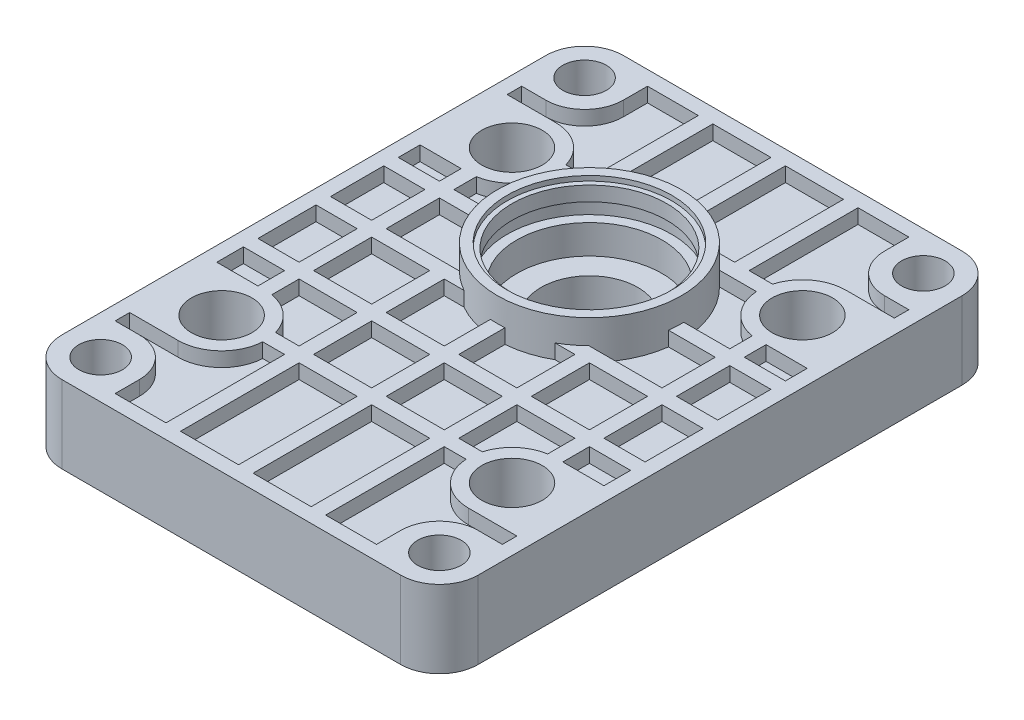
SolidWorks part; units mm, degrees
ref_plane "前视基准面" through (0, 0, 0) normal (0, 0, 1) x (1, 0, 0)
ref_plane "上视基准面" through (0, 0, 0) normal (0, 1, 0) x (1, 0, 0)
ref_plane "右视基准面" through (0, 0, 0) normal (1, 0, 0) x (0, 0, -1)
sketch "草图1" plane through (0, 0, 0) normal (0, 1, 0) x (1, 0, 0)
  line L1 (-43, 58) -> (43, 58)
  line L2 (-43, 58) -> (-43, -58)
  line L3 (-43, -58) -> (43, -58)
  line L4 (43, 58) -> (43, -58)
  line L5 (-43, 58) -> (43, -58) construction
  line L6 (-43, -58) -> (43, 58) construction
  point P0 (0, 0)
  dimension "D1" = 116
  dimension "D2" = 86
extrude "凸台-拉伸1" add sketch "草图1" along normal blind 16
sketch "草图2" plane through (0, 16, 0) normal (0, 1, 0) x (1, 0, 0)
  line L1 (-35, 50) -> (35, 50) construction
  line L2 (-35, 50) -> (-35, -50) construction
  line L3 (-35, -50) -> (35, -50) construction
  line L4 (35, 50) -> (35, -50) construction
  line L5 (-35, 50) -> (35, -50) construction
  line L6 (-35, -50) -> (35, 50) construction
  point P0 (0, 0)
  dimension "D1" = 100
  dimension "D2" = 70
hole_wizard "大小mm 暗销孔1" positions "3D草图1" profile "草图4" hole size "Ø1.0" standard "GB" end condition through all
sketch3d "3D草图1"
  point P0 (-35, 16, -50)
  point P3 (35, 16, -50)
  point P6 (-35, 16, 50)
  point P9 (35, 16, 50)
sketch "草图4" plane through (-35, 16, -50) normal (1, 0, 0) x (0, 0, 1)
  line L0 (0, 0) -> (0, 16)
  line L1 (0, 16) -> (4.5, 16)
  line L2 (4.5, 16) -> (4.5, 0)
  line L5 (4.5, 0) -> (0, 0)
  line L11 (0, -6.35) -> (0, 107.95) construction
  dimension "通孔孔直径" = 9
  dimension "通孔孔深度" = 16
sketch "草图5" plane through (0, 16, 0) normal (0, 1, 0) x (1, 0, 0)
  line L1 (-30, 30) -> (30, 30) construction
  line L2 (-30, 30) -> (-30, -30) construction
  line L3 (-30, -30) -> (30, -30) construction
  line L4 (30, 30) -> (30, -30) construction
  line L5 (-30, 30) -> (30, -30) construction
  line L6 (-30, -30) -> (30, 30) construction
  point P0 (0, 0)
  dimension "D1" = 60
hole_wizard "大小mm 暗销孔2" positions "3D草图2" profile "草图6" hole size "Ø1.0" standard "GB" end condition through all
sketch3d "3D草图2"
  point P0 (-30, 16, -30)
  point P3 (30, 16, -30)
  point P6 (30, 16, 30)
  point P9 (-30, 16, 30)
sketch "草图6" plane through (-30, 16, -30) normal (1, 0, 0) x (0, 0, 1)
  line L0 (0, 0) -> (0, 16)
  line L1 (0, 16) -> (6.25, 16)
  line L2 (6.25, 16) -> (6.25, 0)
  line L5 (6.25, 0) -> (0, 0)
  line L11 (0, -6.35) -> (0, 107.95) construction
  dimension "通孔孔直径" = 12.5
  dimension "通孔孔深度" = 16
sketch "草图7" plane through (0, 16, 0) normal (0, 1, 0) x (1, 0, 0)
  line L0 (0, 0) -> (0, 47.5) construction
  line L1 (0, 0) -> (43, 0) construction
  line L2 (43, -58) -> (43, 58) construction
  line L3 (0, -47.5) -> (0, 0) construction
  point P6 (0, -47.5)
  dimension "D1" = 95
sketch "草图9" plane through (0, 16, 0) normal (0, 1, 0) x (1, 0, 0)
  line L0 (-35, 50) -> (35, 50) construction
  line L1 (0, 50) -> (0, 16) construction
  circle A0 centre (0, 16) radius 22.5 construction
  circle A1 centre (0, 16) radius 19
  dimension "D2" = 45
  dimension "D3" = 38
  dimension "D1" = 34
extrude "凸台-拉伸2" add sketch "草图9" along normal blind 5
sketch "草图10" plane through (0, 21, 0) normal (0, 1, 0) x (1, 0, 0)
  circle A0 centre (0, 16) radius 17
  dimension "D1" = 34
extrude "切除-拉伸1" cut sketch "草图10" against normal blind 1
sketch "草图11" plane through (0, 20, 0) normal (0, 1, 0) x (1, 0, 0)
  circle A0 centre (0, 16) radius 16
  dimension "D1" = 32
extrude "切除-拉伸2" cut sketch "草图11" against normal blind 3
sketch "草图12" plane through (0, 17, 0) normal (0, 1, 0) x (1, 0, 0)
  circle A0 centre (0, 16) radius 17
  dimension "D1" = 34
extrude "切除-拉伸3" cut sketch "草图12" against normal blind 3
sketch "草图13" plane through (0, 14, 0) normal (0, 1, 0) x (1, 0, 0)
  circle A0 centre (0, 16) radius 10
  circle A1 centre (0, 16) radius 16 construction
  dimension "D1" = 20
extrude "切除-拉伸4" cut sketch "草图13" against normal through all
sketch "草图14" plane through (0, 14, 0) normal (0, 1, 0) x (1, 0, 0)
  circle A0 centre (0, 16) radius 15
  dimension "D1" = 30
extrude "切除-拉伸5" cut sketch "草图14" against normal offset from surface (6 mm away) 8 up to face at (0, 0, -6)
sketch "草图15" plane through (0, 16, 0) normal (0, 1, 0) x (1, 0, 0)
  line L0 (0, 58) -> (0, 35) construction
  line L1 (43, 58) -> (-43, 58) construction
  line L2 (-43, -58) -> (43, -58) construction
  line L3 (-1.5, 58) -> (-1.5, 34.9407)
  line L4 (1.5, 58) -> (1.5, 34.9407)
  line L5 (-15, 58) -> (-15, 27.6619)
  line L6 (15, 58) -> (15, 27.6619)
  line L7 (-16.5, 58) -> (-16.5, 25.4207)
  line L8 (13.5, 58) -> (13.5, 29.3697)
  line L9 (-13.5, 58) -> (-13.5, 29.3697)
  line L10 (16.5, 58) -> (16.5, 25.4207)
  line L11 (16.5, 6.5793) -> (16.5, -58)
  line L12 (16.5, 58) -> (16.5, -58) construction
  line L13 (15, 1) -> (15, -58) construction
  line L14 (15, 58) -> (15, -58) construction
  line L15 (13.5, 2.6303) -> (13.5, -58)
  line L16 (13.5, 58) -> (13.5, -58) construction
  line L17 (1.5, -2.9407) -> (1.5, -58)
  line L18 (1.5, 58) -> (1.5, -58) construction
  line L19 (0, -3) -> (0, -58) construction
  line L20 (0, 58) -> (0, -58) construction
  line L21 (-1.5, -2.9407) -> (-1.5, -58)
  line L22 (-1.5, 58) -> (-1.5, -58) construction
  line L23 (-13.5, 2.6303) -> (-13.5, -58)
  line L24 (-13.5, 58) -> (-13.5, -58) construction
  line L25 (-15, 4.3381) -> (-15, -58) construction
  line L26 (-15, 58) -> (-15, -58) construction
  line L27 (-16.5, 6.5793) -> (-16.5, -58)
  line L28 (-16.5, 58) -> (-16.5, -58) construction
  line L29 (43, 16) -> (19, 16) construction
  line L30 (43, -58) -> (43, 58) construction
  line L31 (-19, 16) -> (-43, 16) construction
  line L32 (-43, 58) -> (-43, -58) construction
  line L33 (-11.6619, 1) -> (-43, 1) construction
  line L34 (43, 1) -> (15, 1) construction
  line L35 (43, 1) -> (19, 1) construction
  line L36 (-19, 1) -> (-43, 1) construction
  line L37 (43, -14) -> (1.5, -14) construction
  line L38 (1.5, -14) -> (-43, -14) construction
  line L39 (1.5, -29) -> (-43, -29) construction
  line L40 (43, -29) -> (1.5, -29) construction
  line L41 (-11.6619, -29) -> (-43, -29) construction
  line L42 (-11.6619, -14) -> (-43, -14) construction
  line L43 (43, 1) -> (11.6619, 1) construction
  line L44 (-19, 17.5) -> (-43, 17.5)
  line L45 (-13.3697, 2.5) -> (-43, 2.5)
  line L46 (43, -12.5) -> (1.5, -12.5)
  line L47 (1.5, -12.5) -> (-43, -12.5)
  line L48 (43, -27.5) -> (1.5, -27.5)
  line L49 (1.5, -27.5) -> (-43, -27.5)
  line L50 (43, 2.5) -> (15, 2.5)
  line L51 (43, 17.5) -> (19, 17.5)
  line L52 (-19, 14.5) -> (-43, 14.5)
  line L53 (-9.4207, -0.5) -> (-43, -0.5)
  line L54 (43, -15.5) -> (1.5, -15.5)
  line L55 (1.5, -15.5) -> (-43, -15.5)
  line L56 (43, -30.5) -> (1.5, -30.5)
  line L57 (1.5, -30.5) -> (-43, -30.5)
  line L58 (43, -0.5) -> (15, -0.5)
  line L59 (43, 14.5) -> (19, 14.5)
  line L60 (11.6619, -15.5) -> (-43, -15.5) construction
  line L61 (11.6619, -14) -> (-43, -14) construction
  line L62 (11.6619, -12.5) -> (-43, -12.5) construction
  line L63 (43, -12.5) -> (11.6619, -12.5) construction
  line L64 (43, -14) -> (11.6619, -14) construction
  line L65 (43, -15.5) -> (11.6619, -15.5) construction
  line L66 (11.6619, -30.5) -> (-43, -30.5) construction
  line L67 (11.6619, -29) -> (-43, -29) construction
  line L68 (11.6619, -27.5) -> (-43, -27.5) construction
  line L69 (43, -27.5) -> (11.6619, -27.5) construction
  line L70 (43, -29) -> (11.6619, -29) construction
  line L71 (43, -30.5) -> (11.6619, -30.5) construction
  line L72 (-11.6619, 2.5) -> (-43, 2.5) construction
  line L73 (-11.6619, -0.5) -> (-43, -0.5) construction
  line L74 (-13.3697, 29.5) -> (-43, 29.5)
  line L75 (-11.6619, 31) -> (-43, 31) construction
  line L76 (-9.4207, 32.5) -> (-43, 32.5)
  line L77 (43, 32.5) -> (9.4207, 32.5)
  line L78 (43, 31) -> (11.6619, 31) construction
  line L79 (43, 29.5) -> (13.3697, 29.5)
  line L80 (43, 31) -> (19, 31) construction
  line L81 (-19, 31) -> (-43, 31) construction
  line L82 (43, 32.5) -> (19, 32.5) construction
  line L83 (43, 29.5) -> (19, 29.5) construction
  line L84 (-19, 29.5) -> (-43, 29.5) construction
  line L85 (-19, 32.5) -> (-43, 32.5) construction
  line L86 (40, -55) -> (40, 55)
  line L87 (40, 55) -> (-40, 55)
  line L88 (-40, 55) -> (-40, -55)
  line L89 (-40, -55) -> (40, -55)
  line L90 (43, -58) -> (43, 58)
  line L91 (43, 58) -> (-43, 58)
  line L92 (-43, 58) -> (-43, -58)
  line L93 (-43, -58) -> (43, -58)
  line L94 (43, -58) -> (43, 58)
  line L95 (43, 58) -> (-43, 58)
  line L96 (-43, 58) -> (-43, -58)
  line L97 (-43, -58) -> (43, -58)
  circle A0 centre (0, 16) radius 19 construction
  arc A1 (-16.5, 6.5793) -> (-16.5, 25.4207) centre (0, 16) ccw
  circle A2 centre (0, 16) radius 19 construction
  circle A3 centre (0, 16) radius 19
  circle A4 centre (35, 50) radius 8
  circle A5 centre (-35, 50) radius 8
  circle A6 centre (-35, -50) radius 8
  circle A7 centre (35, -50) radius 8
  dimension "D13" = 0
  dimension "D14" = 16
  dimension "D1" = 1.5
  dimension "D7" = 15
  dimension "D2" = 1.5
  dimension "D3" = 15
  dimension "D4" = 15
  dimension "D5" = 1.5
  dimension "D6" = 1.5
  dimension "D8" = 15
  dimension "D9" = 15
  dimension "D10" = 1.5
  dimension "D11" = 1.5
  dimension "D12" = 15
  dimension "D15" = 3
extrude "切除-拉伸6" cut sketch "草图15" against normal blind 3
sketch "草图16" plane through (0, 16, 0) normal (0, 1, 0) x (1, 0, 0)
  line L0 (16.5, -0.5) -> (9.4207, -0.5)
  line L1 (16.5, 2.5) -> (13.3697, 2.5)
  line L5 (1.5, -12.5) -> (13.5, -12.5)
  line L6 (13.5, -12.5) -> (13.5, 2.6303)
  line L7 (1.5, -2.9407) -> (1.5, -12.5)
  line L8 (1.5, -12.5) -> (13.5, -12.5)
  line L9 (13.5, -12.5) -> (13.5, 2.6303)
  line L10 (1.5, -2.9407) -> (1.5, -12.5)
  arc A0 (1.5, -2.9407) -> (13.5, 2.6303) centre (0, 16) ccw construction
  circle A2 centre (0, 16) radius 17
  circle A3 centre (0, 16) radius 17
  arc A4 (1.5, -2.9407) -> (13.5, 2.6303) centre (0, 16) ccw
  arc A5 (1.5, -2.9407) -> (13.5, 2.6303) centre (0, 16) ccw
  circle A6 centre (0, 16) radius 19
  circle A7 centre (0, 16) radius 19
  dimension "D1" = 0
  dimension "D2" = 0
  dimension "D3" = 0
extrude "凸台-拉伸3" add sketch "草图16" against normal blind 3 contours A5 L0 L9 L1
sketch "草图17" plane through (0, 16, 0) normal (0, 1, 0) x (1, 0, 0)
  line L0 (13.3697, 2.5) -> (16.5, 2.5)
  line L5 (43, -58) -> (43, 58)
  line L6 (16.5, 2.5) -> (40, 2.5)
  line L7 (40, 2.5) -> (40, 29.5)
  line L8 (40, 29.5) -> (36.23, 29.5)
  line L9 (23.77, 29.5) -> (13.3697, 29.5)
  line L10 (16.5, 6.5793) -> (16.5, 2.5)
  line L11 (16.5, 2.5) -> (40, 2.5)
  line L12 (40, 2.5) -> (40, 29.5)
  line L13 (40, 29.5) -> (36.23, 29.5)
  line L14 (23.77, 29.5) -> (13.3697, 29.5)
  line L15 (16.5, 6.5793) -> (16.5, 2.5)
  line L16 (43, 58) -> (-43, 58)
  line L17 (-43, 58) -> (-43, -58)
  line L18 (-43, -58) -> (43, -58)
  line L19 (43, -58) -> (43, 58)
  line L20 (43, 58) -> (-43, 58)
  line L21 (-43, 58) -> (-43, -58)
  line L22 (-43, -58) -> (43, -58)
  circle A1 centre (0, 16) radius 19
  arc A2 (23.77, 29.5) -> (36.23, 29.5) centre (30, 30) ccw
  arc A3 (16.5, 6.5793) -> (13.3697, 29.5) centre (0, 16) ccw
  arc A4 (23.77, 29.5) -> (36.23, 29.5) centre (30, 30) ccw
  arc A5 (16.5, 6.5793) -> (13.3697, 29.5) centre (0, 16) ccw
  circle A6 centre (0, 16) radius 19
  dimension "D1" = 0
  dimension "D2" = 0
  dimension "D3" = 0
extrude "切除-拉伸7" cut sketch "草图17" against normal blind 3 contours A6 L0 L15
fillet "圆角1" radius 8 4 edges at (-43, 8, -58) (43, 8, -58) (43, 8, 58) (-43, 8, 58)
sketch "草图18" plane through (0, 16, 0) normal (0, 1, 0) x (1, 0, 0)
  line L0 (-30, 39) -> (-40, 39)
  line L1 (-40, 43.755) -> (-40, 32.5) construction
  line L2 (-30, 21) -> (-40, 21)
  line L3 (-40, 29.5) -> (-40, 2.5) construction
  line L4 (0, 0) -> (0, 58) construction
  line L5 (35, 58) -> (-35, 58) construction
  line L6 (30, 21) -> (40, 21)
  line L7 (30, 39) -> (40, 39)
  line L8 (-40, 39) -> (-40, 21)
  line L9 (40, 39) -> (40, 21)
  circle A0 centre (-30, 30) radius 9
  circle A1 centre (30, 30) radius 9
  arc A2 (23.77, 29.5) -> (36.23, 29.5) centre (30, 30) ccw construction
  circle A4 centre (30, 30) radius 6.25
  circle A5 centre (-30, 30) radius 6.25
  dimension "D1" = 18
extrude "凸台-拉伸4" add sketch "草图18" against normal blind 3 contours A0 L0 L8 L2 | A1 A4 | A1 L6 L9 L7 | A0 A5
mirror "镜向1" about plane through (0, 0, 0) normal (0, 0, 1) of "凸台-拉伸4"
sketch "草图19" plane through (0, 16, 0) normal (0, 1, 0) x (1, 0, 0)
  line L0 (40, 15) -> (18.9737, 15)
  line L1 (40, 2.5) -> (40, 21) construction
  line L2 (-40, 21) -> (-40, 2.5) construction
  line L3 (-13.3697, 2.5) -> (-40, 2.5) construction
  line L4 (40, 16.5) -> (18.9934, 16.5)
  line L5 (40, 13.5) -> (18.8348, 13.5)
  line L6 (-18.8348, 13.5) -> (-40, 13.5)
  line L7 (40, 13.5) -> (-40, 13.5) construction
  line L8 (-18.9737, 15) -> (-40, 15)
  line L9 (40, 15) -> (-40, 15) construction
  line L10 (-18.9934, 16.5) -> (-40, 16.5)
  line L11 (40, 16.5) -> (-40, 16.5) construction
  line L12 (-40, 16.5) -> (-40, 13.5)
  line L13 (40, 16.5) -> (40, 13.5)
  line L16 (35, 58) -> (-35, 58)
  line L17 (-43, 50) -> (-43, -50)
  line L18 (-35, -58) -> (35, -58)
  line L19 (43, -50) -> (43, 50)
  line L20 (35, 58) -> (-35, 58)
  line L21 (-43, 50) -> (-43, -50)
  line L22 (-35, -58) -> (35, -58)
  line L23 (43, -50) -> (43, 50)
  circle A1 centre (0, 16) radius 19
  circle A2 centre (0, 16) radius 19
  arc A6 (-35, 58) -> (-43, 50) centre (-35, 50) ccw
  arc A7 (-43, -50) -> (-35, -58) centre (-35, -50) ccw
  arc A8 (35, -58) -> (43, -50) centre (35, -50) ccw
  arc A9 (43, 50) -> (35, 58) centre (35, 50) ccw
  arc A10 (-35, 58) -> (-43, 50) centre (-35, 50) ccw
  arc A11 (-43, -50) -> (-35, -58) centre (-35, -50) ccw
  arc A12 (35, -58) -> (43, -50) centre (35, -50) ccw
  arc A13 (43, 50) -> (35, 58) centre (35, 50) ccw
  dimension "D1" = 12.5
  dimension "D2" = 1.5
  dimension "D3" = 1.5
  dimension "D4" = 0
  dimension "D5" = 0
extrude "凸台-拉伸5" add sketch "草图19" against normal blind 3 contours A2 L0 L13 L4 | A2 L5 L13 L0 | A2 L10 L12 L8 | A2 L8 L12 L6
sketch "草图20" plane through (0, 16, 0) normal (0, 1, 0) x (1, 0, 0)
  line L0 (-30, 23.75) -> (-30, -23.75)
  line L1 (30, 21) -> (30, -21)
  line L2 (-31.5, 23.75) -> (-31.5, -23.75)
  line L3 (28.5, 21.1259) -> (28.5, -21.1259)
  line L4 (-28.5, 23.75) -> (-28.5, -23.75)
  line L5 (31.5, 21) -> (31.5, -21)
  line L6 (35, -42) -> (40, -42)
  line L7 (40, -43.755) -> (40, -39) construction
  line L8 (27, -50) -> (27, -55)
  line L9 (16.5, -55) -> (28.755, -55) construction
  line L10 (35, 58) -> (-35, 58)
  line L11 (-43, 50) -> (-43, -50)
  line L12 (-35, -58) -> (35, -58)
  line L13 (43, -50) -> (43, 50)
  line L14 (35, 58) -> (-35, 58)
  line L15 (-43, 50) -> (-43, -50)
  line L16 (-35, -58) -> (35, -58)
  line L17 (43, -50) -> (43, 50)
  line L18 (-27, -50) -> (-27, -58)
  line L19 (-35, -42) -> (-43, -42)
  line L20 (-35, 42) -> (-43, 42)
  line L21 (-27, 50) -> (-27, 58)
  line L22 (27, 50) -> (27, 58)
  line L23 (35, 42) -> (43, 42)
  line L24 (-28.755, -55) -> (-16.5, -55) construction
  line L25 (-40, -39) -> (-40, -43.755) construction
  line L26 (16.5, -55) -> (28.755, -55) construction
  line L27 (40, 39) -> (40, 43.755) construction
  line L28 (28.755, 55) -> (16.5, 55) construction
  line L29 (-40, 43.755) -> (-40, 39) construction
  line L30 (-16.5, 55) -> (-28.755, 55) construction
  line L31 (-28.755, -55) -> (-16.5, -55)
  line L32 (-40, -39) -> (-40, -43.755)
  line L33 (16.5, -55) -> (28.755, -55)
  line L34 (40, -43.755) -> (40, -39)
  line L35 (40, 39) -> (40, 43.755)
  line L36 (28.755, 55) -> (16.5, 55)
  line L37 (-40, 43.755) -> (-40, 39)
  line L38 (-16.5, 55) -> (-28.755, 55)
  line L39 (-30, -21) -> (-40, -21) construction
  line L40 (-30, 21) -> (-40, 21) construction
  line L41 (30, 21) -> (40, 21) construction
  line L42 (30, -21) -> (40, -21) construction
  line L43 (-30, -21) -> (-40, -21)
  line L44 (-30, 21) -> (-40, 21)
  line L45 (30, 21) -> (40, 21)
  line L46 (30, -21) -> (40, -21)
  line L47 (28.5, 21) -> (28.5, -21) construction
  circle A0 centre (-30, 30) radius 6.25 construction
  circle A1 centre (-30, -30) radius 6.25 construction
  arc A2 (30, -21) -> (21.3542, -27.5) centre (30, -30) ccw construction
  arc A3 (28.755, 55) -> (40, 43.755) centre (35, 50) ccw construction
  arc A4 (-40, 43.755) -> (-28.755, 55) centre (-35, 50) ccw construction
  arc A5 (-28.755, -55) -> (-40, -43.755) centre (-35, -50) ccw construction
  arc A6 (40, -43.755) -> (28.755, -55) centre (35, -50) ccw construction
  arc A7 (-35, 58) -> (-43, 50) centre (-35, 50) ccw
  arc A8 (-43, -50) -> (-35, -58) centre (-35, -50) ccw
  arc A9 (35, -58) -> (43, -50) centre (35, -50) ccw
  arc A10 (43, 50) -> (35, 58) centre (35, 50) ccw
  arc A11 (-35, 58) -> (-43, 50) centre (-35, 50) ccw
  arc A12 (-43, -50) -> (-35, -58) centre (-35, -50) ccw
  arc A13 (35, -58) -> (43, -50) centre (35, -50) ccw
  arc A14 (43, 50) -> (35, 58) centre (35, 50) ccw
  arc A15 (27, 50) -> (35, 42) centre (35, 50) ccw
  arc A16 (-35, 42) -> (-27, 50) centre (-35, 50) ccw
  arc A17 (-27, -50) -> (-35, -42) centre (-35, -50) ccw
  arc A18 (35, -42) -> (27, -50) centre (35, -50) ccw
  arc A19 (-28.755, -55) -> (-40, -43.755) centre (-35, -50) ccw construction
  arc A20 (-40, 43.755) -> (-28.755, 55) centre (-35, 50) ccw construction
  arc A21 (-28.755, -55) -> (-40, -43.755) centre (-35, -50) ccw
  arc A22 (40, -43.755) -> (28.755, -55) centre (35, -50) ccw
  arc A23 (-40, 43.755) -> (-28.755, 55) centre (-35, 50) ccw
  arc A24 (28.755, 55) -> (40, 43.755) centre (35, 50) ccw
  arc A25 (-21.3542, -27.5) -> (-30, -21) centre (-30, -30) ccw construction
  arc A26 (-30, 21) -> (-21.0139, 29.5) centre (-30, 30) ccw construction
  arc A27 (21.0139, 29.5) -> (30, 21) centre (30, 30) ccw construction
  arc A28 (30, -21) -> (21.3542, -27.5) centre (30, -30) ccw construction
  circle A29 centre (30, 30) radius 6.25 construction
  arc A30 (-21.3542, -27.5) -> (-30, -21) centre (-30, -30) ccw
  arc A31 (-30, 21) -> (-21.0139, 29.5) centre (-30, 30) ccw
  arc A32 (21.0139, 29.5) -> (30, 21) centre (30, 30) ccw
  arc A33 (30, -21) -> (21.3542, -27.5) centre (30, -30) ccw
  circle A34 centre (30, 30) radius 6.25
  circle A35 centre (-30, -30) radius 6.25
  circle A36 centre (-30, 30) radius 6.25
  dimension "D1" = 1.5
  dimension "D2" = 1.5
  dimension "D3" = 0
extrude "凸台-拉伸6" add sketch "草图20" against normal blind 3 contours A33 L1 A32 L3 | L1 L46 L5 L45 | L0 L44 L2 L43 | A31 L0 A30 L4 | A23 L37 L20 | A23 L21 L38 | A24 L36 L22 | A24 L23 L35 | A22 L34 L6 | A22 L8 L33 | A21 L31 L18 | A21 L19 L32
sketch "草图21" plane through (0, 0, 0) normal (0, -1, 0) x (1, 0, 0)
  line L0 (43, 0) -> (0, 0) construction
  line L1 (43, 50) -> (43, -50) construction
  line L2 (0, -47.5) -> (0, 47.5) construction
  dimension "D1" = 95
hole_wizard "大小mm 暗销孔4" positions "3D草图4" profile "草图22" hole size "Ø8.0" standard "GB"
sketch3d "3D草图4"
  point P0 (0, 0, 47.5)
  point P3 (0, 0, -47.5)
sketch "草图22" plane through (0, 0, 47.5) normal (1, 0, 0) x (0, 0, -1)
  line L0 (0, 0) -> (0, 9.4034)
  line L1 (0, 9.4034) -> (4, 7)
  line L2 (4, 7) -> (4, 0)
  line L5 (4, 0) -> (0, 0)
  line L10 (0, 9.4034) -> (-4, 7) construction
  line L11 (0, -6.35) -> (0, 107.95) construction
  dimension "孔直径" = 8
  dimension "孔深度" = 7
  dimension "导头角度" = 118
